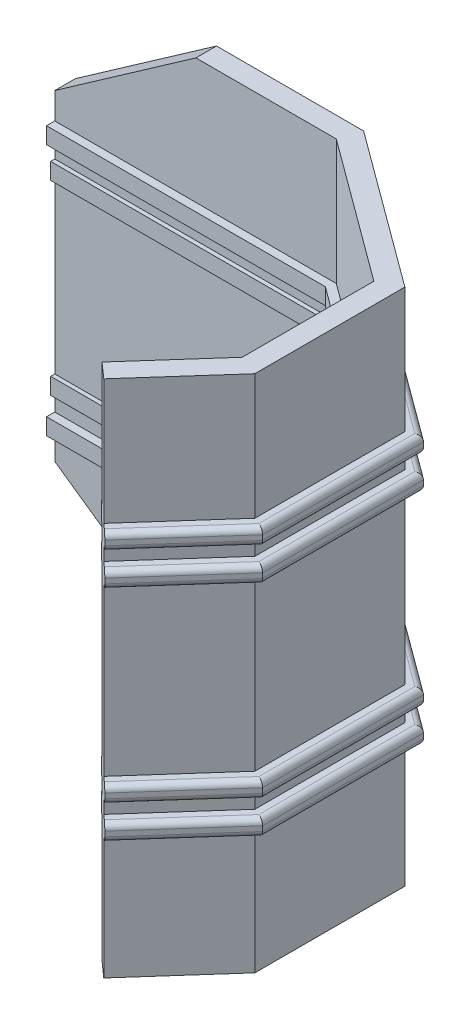
SolidWorks part; units mm, degrees
ref_plane "前视基准面" through (0, 0, 0) normal (0, 0, 1) x (1, 0, 0)
ref_plane "上视基准面" through (0, 0, 0) normal (0, 1, 0) x (1, 0, 0)
ref_plane "右视基准面" through (0, 0, 0) normal (1, 0, 0) x (0, 0, -1)
sketch "草图1" plane through (0, 0, 0) normal (0, 1, 0) x (1, 0, 0)
  line L0 (0, -8) -> (0, 8)
  line L1 (0, 8) -> (-17.2409, 20.6772)
  line L2 (0, -8) -> (-8, -17)
  line L3 (2.5, -8.9505) -> (-6.1315, -18.6609)
  line L4 (2.5, -8.9505) -> (2.5, 9.2648)
  line L5 (2.5, 9.2648) -> (-16.4207, 23.1772)
  line L6 (-6.1315, -18.6609) -> (-8, -17)
  line L7 (-17.2409, 20.6772) -> (-51.4207, 20.6772)
  line L8 (-51.4207, 23.1772) -> (-16.4207, 23.1772)
  line L9 (2.5, 9.2648) -> (-15.76, 22.6913) construction
  line L10 (-51.4207, 23.1772) -> (-51.4207, 20.6772)
  dimension "D1" = 16
  dimension "D2" = 21.4
  dimension "D3" = 126.327
  dimension "D4" = 9
  dimension "D5" = 8
  dimension "D7" = 2.5
  dimension "D8" = 35
  dimension "D6" = 2.5
extrude "凸台-拉伸1" add sketch "草图1" along normal blind 31.5 and the other way blind 31.5
chamfer "倒角1" distance 12 angle 55 2 edges at (-51.4207, -31.5, -21.9272) (-51.4207, 31.5, -21.9272) first distance on face at (-51.4207, 0, -21.9272)
ref_plane "基准面1" through (0, 12.3, 0) normal (0, 1, 0) x (1, 0, 0)
sketch "草图4" plane through (0, 12.3, 0) normal (0, 1, 0) x (1, 0, 0)
  line L0 (2.5, 9.2648) -> (-16.4207, 23.1772) construction
  line L1 (2.5, 9.2648) -> (-16.4207, 23.1772)
  line L2 (-6.1315, -18.6609) -> (2.5, -8.9505) construction
  line L3 (2.5, -8.9505) -> (2.5, 9.2648) construction
  line L4 (-16.4207, 23.1772) -> (-34.283, 23.1772) construction
  line L5 (-51.4207, 23.1772) -> (-34.283, 23.1772) construction
  line L6 (-6.1315, -18.6609) -> (2.5, -8.9505)
  line L7 (2.5, -8.9505) -> (2.5, 9.2648)
  line L8 (-16.4207, 23.1772) -> (-34.283, 23.1772)
  line L9 (-51.4207, 23.1772) -> (-34.283, 23.1772)
  line L10 (-5.0104, -19.6575) -> (4, -9.5208)
  line L11 (4, -9.5208) -> (4, 10.0238)
  line L12 (4, 10.0238) -> (-15.9286, 24.6772)
  line L13 (-15.9286, 24.6772) -> (-34.283, 24.6772)
  line L14 (-51.4207, 24.6772) -> (-34.283, 24.6772)
  dimension "D1" = 1.5
extrude "拉伸-薄壁1" add sketch "草图4" against normal blind 2 thin thin type one direction wall 3
ref_plane "基准面2" through (0, 16.3, 0) normal (0, 1, 0) x (1, 0, 0)
sketch "草图5" plane through (0, 16.3, 0) normal (0, 1, 0) x (1, 0, 0)
  line L0 (-6.1315, -18.6609) -> (2.5, -8.9505) construction
  line L1 (2.5, -8.9505) -> (2.5, 9.2648) construction
  line L2 (2.5, 9.2648) -> (-16.4207, 23.1772) construction
  line L3 (-16.4207, 23.1772) -> (-34.283, 23.1772) construction
  line L4 (-51.4207, 23.1772) -> (-34.283, 23.1772) construction
  line L5 (-6.1315, -18.6609) -> (2.5, -8.9505)
  line L6 (2.5, -8.9505) -> (2.5, 9.2648)
  line L7 (2.5, 9.2648) -> (-16.4207, 23.1772)
  line L8 (-16.4207, 23.1772) -> (-34.283, 23.1772)
  line L9 (-51.4207, 23.1772) -> (-34.283, 23.1772)
  line L10 (-5.0104, -19.6575) -> (4, -9.5208)
  line L11 (4, -9.5208) -> (4, 10.0238)
  line L12 (4, 10.0238) -> (-15.9286, 24.6772)
  line L13 (-15.9286, 24.6772) -> (-34.283, 24.6772)
  line L14 (-51.4207, 24.6772) -> (-34.283, 24.6772)
  dimension "D1" = 1.5
extrude "拉伸-薄壁2" add sketch "草图5" against normal blind 2 thin thin type one direction wall 3.5
fillet "圆角1" radius 0.7 16 edges at (-0.5052, 10.3, 14.5891) (4, 10.3, -0.2515) (-5.9643, 10.3, -17.3505) (-33.6747, 10.3, -24.6772) (-0.5052, 12.3, 14.5891) (4, 12.3, -0.2515) (-5.9643, 12.3, -17.3505) (-33.6747, 12.3, -24.6772) (-33.6747, 14.3, -24.6772) (-5.9643, 14.3, -17.3505) (4, 14.3, -0.2515) (-0.5052, 14.3, 14.5891) (-0.5052, 16.3, 14.5891) (4, 16.3, -0.2515) (-5.9643, 16.3, -17.3505) (-33.6747, 16.3, -24.6772)
mirror "镜向1" about plane through (0, 0, 0) normal (0, 1, 0) of "拉伸-薄壁2", "圆角1", "拉伸-薄壁1"
